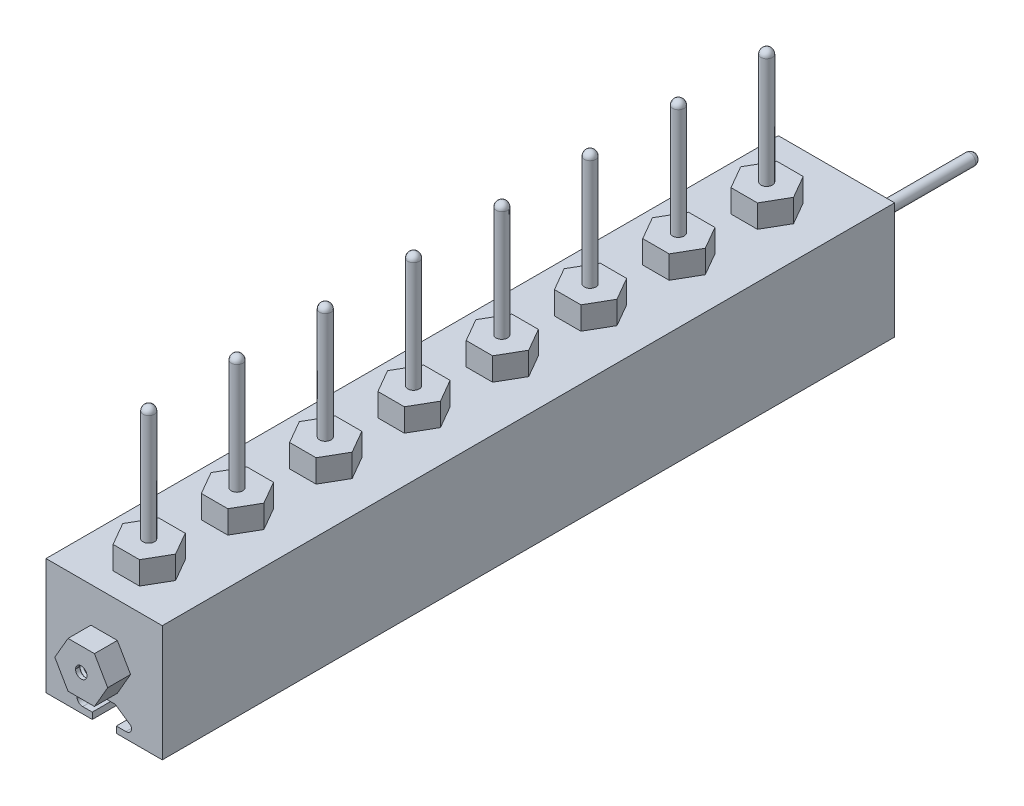
SolidWorks part; units mm, degrees
ref_plane "Front Plane" through (0, 0, 0) normal (0, 0, 1) x (1, 0, 0)
ref_plane "Top Plane" through (0, 0, 0) normal (0, 1, 0) x (1, 0, 0)
ref_plane "Right Plane" through (0, 0, 0) normal (1, 0, 0) x (0, 0, -1)
sketch "Sketch1" plane through (0, 0, 0) normal (0, 1, 0) x (1, 0, 0)
  line L1 (-12.7, -80) -> (12.7, -80)
  line L2 (-12.7, -80) -> (-12.7, 80)
  line L3 (-12.7, 80) -> (12.7, 80)
  line L4 (12.7, -80) -> (12.7, 80)
  line L5 (-12.7, -80) -> (12.7, 80) construction
  line L6 (-12.7, 80) -> (12.7, -80) construction
  point P0 (0, 0)
  dimension "D1" = 25.4
  dimension "D2" = 160
extrude "Boss-Extrude1" add sketch "Sketch1" along normal blind 25.4
sketch "Sketch2" plane through (0, 25.4, 0) normal (0, 1, 0) x (1, 0, 0)
  line L1 (5.6126, 65) -> (2.7259, 70)
  line L2 (2.7259, 70) -> (-3.0476, 70)
  line L3 (-3.0476, 70) -> (-5.9344, 65)
  line L4 (-5.9344, 65) -> (-3.0476, 60)
  line L5 (-3.0476, 60) -> (2.7259, 60)
  line L6 (2.7259, 60) -> (5.6126, 65)
  line L7 (12.7, 80) -> (-12.7, 80) construction
  circle A0 centre (-0.1609, 65) radius 5 construction
  dimension "D1" = 10
  dimension "D2" = 10
extrude "Boss-Extrude2" add sketch "Sketch2" along normal blind 5
pattern_linear "LPattern1" count 8 spacing 19.2857 along (0, 0, 1) of "Boss-Extrude2"
sketch "Sketch3" plane through (0, 0, -80) normal (0, 0, -1) x (-1, 0, 0)
  line L0 (-12.7, 25.4) -> (12.7, 25.4) construction
  line L1 (-2.8868, 7.7) -> (2.8868, 7.7)
  line L2 (2.8868, 7.7) -> (5.7735, 12.7)
  line L3 (5.7735, 12.7) -> (2.8868, 17.7)
  line L4 (2.8868, 17.7) -> (-2.8868, 17.7)
  line L5 (-2.8868, 17.7) -> (-5.7735, 12.7)
  line L6 (-5.7735, 12.7) -> (-2.8868, 7.7)
  circle A0 centre (0, 12.7) radius 5 construction
  dimension "D1" = 7.7
  dimension "D2" = 10
extrude "Boss-Extrude3" add sketch "Sketch3" along normal blind 5
sketch "Sketch4" plane through (0, 0, 80) normal (0, 0, 1) x (1, 0, 0)
  line L0 (-12.7, 25.4) -> (12.7, 25.4) construction
  line L1 (5.7735, 12.7) -> (2.8868, 17.7)
  line L2 (2.8868, 17.7) -> (-2.8868, 17.7)
  line L3 (-2.8868, 17.7) -> (-5.7735, 12.7)
  line L4 (-5.7735, 12.7) -> (-2.8868, 7.7)
  line L5 (-2.8868, 7.7) -> (2.8868, 7.7)
  line L6 (2.8868, 7.7) -> (5.7735, 12.7)
  circle A0 centre (0, 12.7) radius 5 construction
  dimension "D2" = 10
  dimension "D1" = 7.7
extrude "Boss-Extrude4" add sketch "Sketch4" along normal blind 5
sketch "Sketch8" plane through (0, 0, -80) normal (0, 0, -1) x (-1, 0, 0)
  line L0 (-2.667, 0) -> (-2.667, 1.3992)
  line L1 (-2.667, 1.3992) -> (-6.037, 1.3992)
  line L2 (-6.037, 1.3992) -> (-6.037, 2.8992)
  line L3 (-6.037, 2.8992) -> (-2.422, 5.3899)
  line L4 (-2.422, 5.3899) -> (2.348, 5.3899)
  line L5 (2.348, 5.3899) -> (5.963, 2.8992)
  line L6 (5.963, 2.8992) -> (5.963, 1.3992)
  line L7 (5.963, 1.3992) -> (2.593, 1.3992)
  line L8 (2.593, 1.3992) -> (2.593, 0)
  line L9 (2.593, 0) -> (-2.667, 0)
  line L10 (-12.7, 0) -> (12.7, 0) construction
  line L11 (-12.7, 25.4) -> (-12.7, 0) construction
  dimension "D1" = 0
  dimension "D2" = 5.26
  dimension "D3" = 4.39
  dimension "D4" = 4.39
  dimension "D5" = 4.77
  dimension "D6" = 1.5
  dimension "D7" = 1.5
  dimension "D8" = 0
  dimension "D9" = 3.37
  dimension "D10" = 3.37
  dimension "D11" = 10.033
extrude "Cut-Extrude1" cut sketch "Sketch8" against normal through all both and the other way through all
fillet "Fillet1" radius 1.27 2 edges at (6.037, 1.3992, 0) (-5.963, 1.3992, 0)
fillet "Fillet2" radius 0.762 2 edges at (-2.348, 5.3899, 0) (2.422, 5.3899, 0)
fillet "Fillet3" radius 0.762 2 edges at (6.037, 2.8992, 0) (-5.963, 2.8992, 0)
sketch "Sketch9" plane through (0, 30.4, 0) normal (0, 1, 0) x (1, 0, 0)
  line L0 (2.7259, 70) -> (-3.0476, 70) construction
  circle A0 centre (-0.2554, 65) radius 1.25
  dimension "D1" = 2.5
  dimension "D2" = 5
extrude "Boss-Extrude5" add sketch "Sketch9" along normal blind 25.4
fillet "Fillet4" radius 1.25 1 edges at (-0.2554, 55.8, -63.75)
pattern_linear "LPattern2" count 8 spacing 19.2857 along (0, 0, 1) of "Boss-Extrude5"
fillet "Fillet5" radius 1.25 7 edges at (-0.2554, 55.8, -44.4643) (-0.2554, 55.8, 71.25) (-0.2554, 55.8, 51.9643) (-0.2554, 55.8, 32.6786) (-0.2554, 55.8, 13.3929) (-0.2554, 55.8, -5.8929) (-0.2554, 55.8, -25.1786)
sketch "Sketch10" plane through (0, 0, -85) normal (0, 0, -1) x (-1, 0, 0)
  line L0 (2.8868, 17.7) -> (-2.8868, 17.7) construction
  circle A0 centre (0, 12.7) radius 1.25
  dimension "D1" = 2.5
  dimension "D2" = 5
extrude "Boss-Extrude6" add sketch "Sketch10" along normal blind 25.4
fillet "Fillet6" radius 1.25 1 edges at (-1.25, 12.7, -110.4)
sketch "Sketch11" plane through (0, 0, 85) normal (0, 0, 1) x (1, 0, 0)
  line L0 (2.8868, 17.7) -> (-2.8868, 17.7) construction
  circle A0 centre (0, 12.7) radius 1.25
  dimension "D1" = 2.5
  dimension "D2" = 5
extrude "Cut-Extrude2" cut sketch "Sketch11" against normal blind 25.4
thread "Thread1" pitch 1 method cut profile "Thread Profile1" start angle 0, offset 0, length 10, pitch 1, diameter 2.5
ref_plane "Plane3" through (-1.25, 12.7, 85) normal (0, -1, 0) x (-1, 0, 0)
sketch "Thread Profile1" plane through (-1.25, 12.7, 85) normal (0, -1, 0) x (-1, 0, 0)
  line L0 (0, 0) -> (0, 1) construction
  line L1 (0, 0) -> (0.5413, 0.3125)
  line L2 (0.5413, 0.3125) -> (0.5413, 0.4375)
  line L3 (0.5413, 0.4375) -> (0, 0.75)
  line L4 (0.5413, 0.375) -> (0, 0.375) construction
  line L11 (0, 0) -> (0, 0.75)
  point P2 (0, 0)
  dimension "Pitch" = 1
  dimension "Profile_Angle" = 60
  dimension "Profile_Land" = 0.125
  dimension "Profile_Height" = 0.5413
